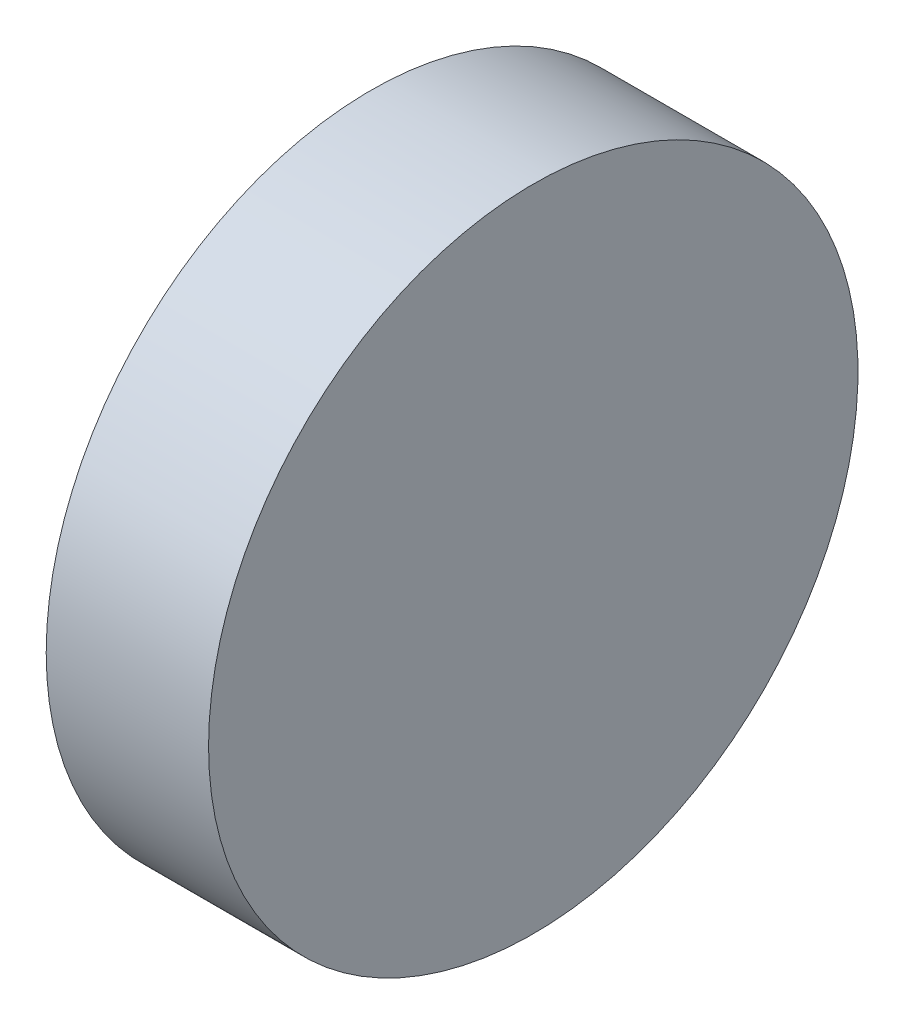
SolidWorks part; units mm, degrees
material "6061-T6 (SS)"
ref_plane "Front Plane" through (0, 0, 0) normal (0, 0, 1) x (1, 0, 0)
ref_plane "Top Plane" through (0, 0, 0) normal (0, 1, 0) x (1, 0, 0)
ref_plane "Right Plane" through (0, 0, 0) normal (1, 0, 0) x (0, 0, -1)
sketch "Sketch1" plane through (0, 0, 0) normal (1, 0, 0) x (0, 0, -1)
  circle A0 centre (0, 0) radius 9.525
  dimension "D1" = 19.05
extrude "Boss-Extrude1" add sketch "Sketch1" along normal blind 4.7625
